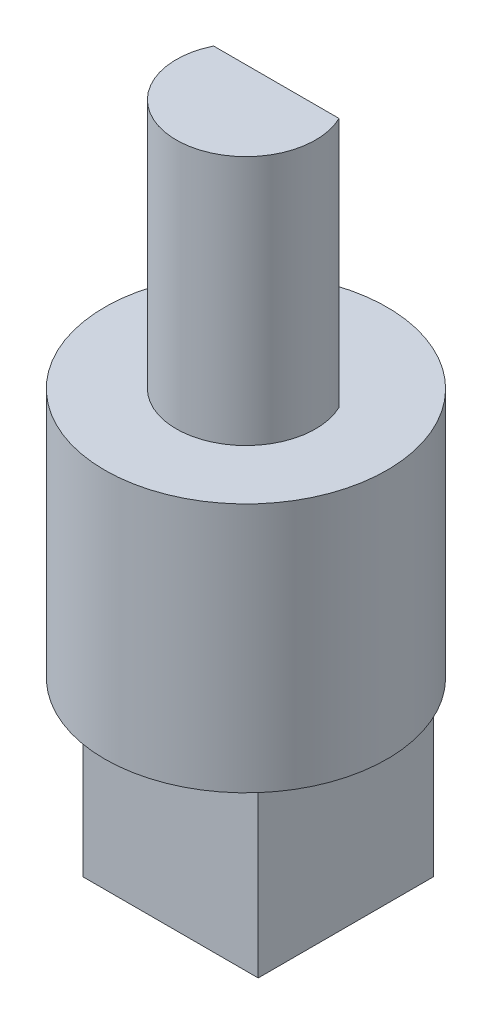
SolidWorks part; units mm, degrees
ref_plane "Front Plane" through (0, 0, 0) normal (0, 0, 1) x (1, 0, 0)
ref_plane "Top Plane" through (0, 0, 0) normal (0, 1, 0) x (1, 0, 0)
ref_plane "Right Plane" through (0, 0, 0) normal (1, 0, 0) x (0, 0, -1)
sketch "Sketch1" plane through (0, 0, 0) normal (0, 1, 0) x (1, 0, 0)
  line L7 (2.45, -2.1069) -> (-2.45, -2.1069)
  line L8 (2.45, -2.1069) -> (2.45, 2.7931)
  line L9 (2.45, 2.7931) -> (-2.45, 2.7931)
  line L10 (-2.45, -2.1069) -> (-2.45, 2.7931)
  line L11 (2.45, -2.1069) -> (-2.45, 2.7931) construction
  line L12 (2.45, 2.7931) -> (-2.45, -2.1069) construction
  point P0 (0, 0)
  dimension "D1" = 4.9
  dimension "D4" = 90
extrude "Boss-Extrude1" add sketch "Sketch1" along normal blind 5
sketch "Sketch2" plane through (0, 5, 0) normal (0, 1, 0) x (1, 0, 0)
  circle A1 centre (0, 0) radius 3.95
  dimension "D1" = 7.9
extrude "Boss-Extrude2" add sketch "Sketch2" along normal blind 7
sketch "Sketch3" plane through (0, 12, 0) normal (0, 1, 0) x (1, 0, 0)
  circle A0 centre (0, 0) radius 1.95
  dimension "D1" = 3.9
extrude "Boss-Extrude3" add sketch "Sketch3" along normal blind 7
sketch "Sketch4" plane through (0, 19, 0) normal (0, 1, 0) x (1, 0, 0)
  line L0 (0, -1.95) -> (0, 0.85) construction
  line L1 (0, 0.85) -> (1.755, 0.85) construction
  line L2 (0, 0.85) -> (-1.755, 0.85) construction
  line L3 (-1.755, 0.85) -> (1.755, 0.85)
  circle A0 centre (0, 0) radius 1.95 construction
  circle A1 centre (0, 0) radius 1.95 construction
  arc A2 (-1.755, 0.85) -> (1.755, 0.85) centre (0, 0) cw
  dimension "D1" = 2.8
extrude "Cut-Extrude1" cut sketch "Sketch4" against normal blind 7
